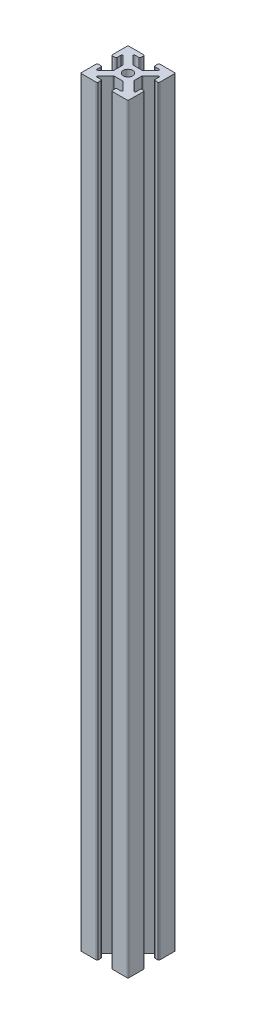
SolidWorks part; units mm, degrees
ref_plane "Plan de face" through (0, 0, 0) normal (0, 0, 1) x (1, 0, 0)
ref_plane "Plan de dessus" through (0, 0, 0) normal (0, 1, 0) x (1, 0, 0)
ref_plane "Plan de droite" through (0, 0, 0) normal (1, 0, 0) x (0, 0, -1)
sketch "Esquisse1" plane through (0, 0, 0) normal (0, 1, 0) x (1, 0, 0)
  line L0 (0, 0) -> (20, 0) construction
  line L1 (20, 0) -> (20, 20) construction
  line L2 (20, 20) -> (0, 20) construction
  line L3 (0, 20) -> (0, 0) construction
  line L4 (0, 0) -> (20, 20) construction
  line L5 (20, 20) -> (0, 20) construction
  line L6 (0, 20) -> (20, 0) construction
  line L7 (0, 0) -> (0, 7)
  line L8 (0, 20) -> (0, 13)
  line L9 (0, 20) -> (7, 20)
  line L10 (20, 20) -> (20, 13)
  line L11 (20, 20) -> (13, 20)
  line L12 (20, 0) -> (20, 7)
  line L13 (20, 0) -> (13, 0)
  line L14 (0, 0) -> (7, 0)
  line L15 (0, 7) -> (2, 7)
  line L16 (0, 13) -> (2, 13)
  line L17 (2, 13) -> (2, 16)
  line L18 (7, 0) -> (7, 2)
  line L19 (13, 0) -> (13, 2)
  line L20 (13, 2) -> (16, 2)
  line L21 (20, 7) -> (18.5, 7)
  line L22 (18.5, 7) -> (18.5, 4)
  line L23 (20, 13) -> (18, 13)
  line L24 (18, 13) -> (18, 16)
  line L25 (13, 20) -> (13, 18)
  line L26 (13, 18) -> (16, 18)
  line L27 (7, 20) -> (7, 18)
  line L28 (7, 18) -> (4, 18)
  line L29 (10, 10) -> (10, 14) construction
  line L30 (10, 14) -> (14, 14) construction
  line L31 (14, 14) -> (14, 6) construction
  line L32 (14, 6) -> (6, 6) construction
  line L33 (6, 6) -> (6, 14) construction
  line L34 (6, 14) -> (10, 14) construction
  line L42 (7, 2) -> (4, 2)
  line L44 (2, 7) -> (2, 4)
  line L49 (2, 4) -> (6, 8)
  line L50 (4, 2) -> (8, 6)
  line L51 (8, 6) -> (12, 6)
  line L52 (12, 6) -> (16, 2)
  line L53 (2, 16) -> (6, 12)
  line L54 (6, 12) -> (6, 8)
  line L55 (18.5, 4) -> (14, 8.5)
  line L56 (14, 8.5) -> (14, 12)
  line L57 (14, 12) -> (18, 16)
  line L58 (16, 18) -> (12, 14)
  line L59 (12, 14) -> (8, 14)
  line L60 (8, 14) -> (4, 18)
  circle A0 centre (10, 10) radius 2
extrude "Boss.-Extru.1" add sketch "Esquisse1" along normal blind 320
fillet "Congé1" radius 0.4 36 edges at (4, 160, -18) (2, 160, -16) (6, 160, -12) (6, 160, -8) (2, 160, -4) (2, 160, -7) (0, 160, -7) (0, 160, 0) (7, 160, 0) (7, 160, -2) (4, 160, -2) (8, 160, -6) (12, 160, -6) (16, 160, -2) (13, 160, -2) (13, 160, 0) (20, 160, 0) (20, 160, -7) (18.5, 160, -7) (18.5, 160, -4) (14, 160, -8.5) (14, 160, -12) (18, 160, -16) (18, 160, -13) (20, 160, -13) (20, 160, -20) (13, 160, -20) (13, 160, -18) (16, 160, -18) (12, 160, -14) (8, 160, -14) (7, 160, -18) (7, 160, -20) (0, 160, -20) (0, 160, -13) (2, 160, -13) first distance on face at (6, 160, -16) first distance on face at (2, 160, -14.5) first distance on face at (4, 160, -14) first distance on face at (6, 160, -10) first distance on face at (4, 160, -6) first distance on face at (2, 160, -5.5) first distance on face at (1, 160, -7) first distance on face at (0, 160, -3.5) first distance on face at (3.5, 160, 0) first distance on face at (7, 160, -1) first distance on face at (5.5, 160, -2) first distance on face at (6, 160, -4) first distance on face at (10, 160, -6) first distance on face at (14, 160, -4) first distance on face at (14.5, 160, -2) first distance on face at (13, 160, -1) first distance on face at (16.5, 160, 0) first distance on face at (20, 160, -3.5) first distance on face at (19.25, 160, -7) first distance on face at (18.5, 160, -5.5) first distance on face at (16.25, 160, -6.25) first distance on face at (14, 160, -10.25) first distance on face at (16, 160, -14) first distance on face at (18, 160, -14.5) first distance on face at (19, 160, -13) first distance on face at (20, 160, -16.5) first distance on face at (16.5, 160, -20) first distance on face at (13, 160, -19) first distance on face at (14.5, 160, -18) first distance on face at (14, 160, -16) first distance on face at (10, 160, -14) first distance on face at (5.5, 160, -18) first distance on face at (7, 160, -19) first distance on face at (3.5, 160, -20) first distance on face at (0, 160, -16.5) first distance on face at (1, 160, -13)
